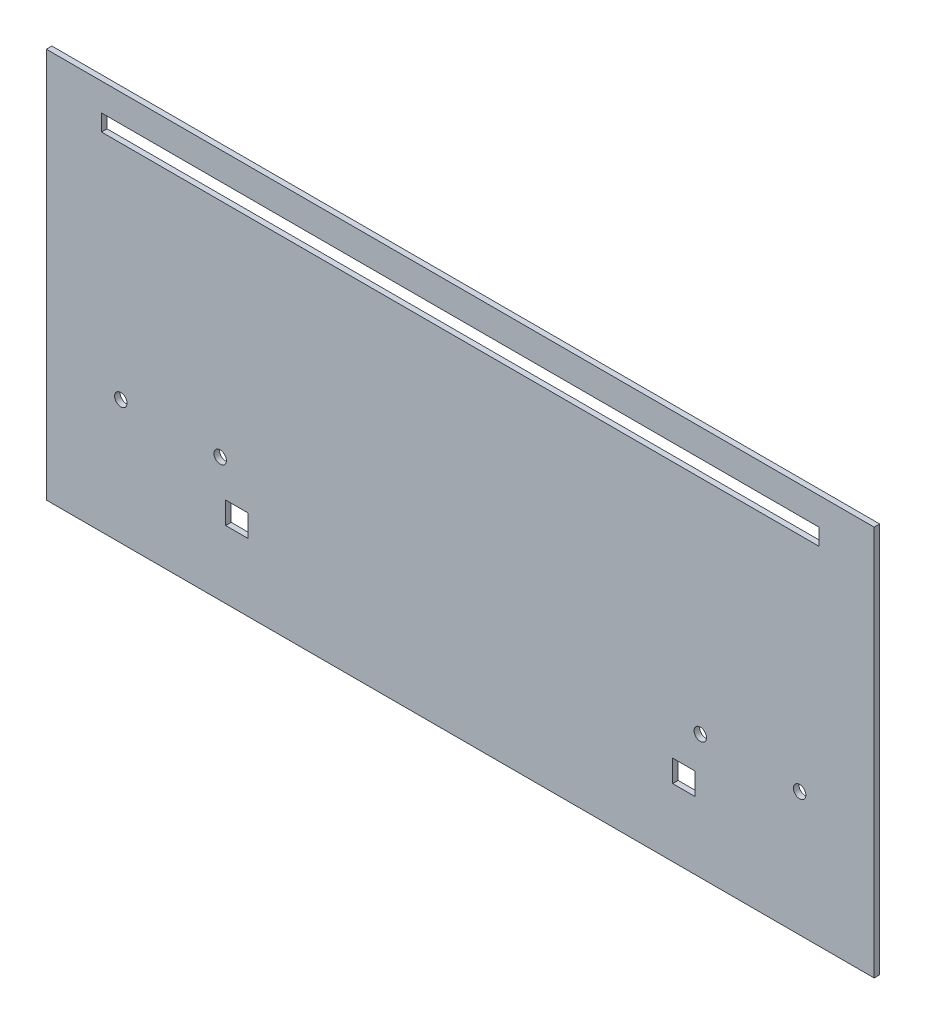
SolidWorks part; units mm, degrees
ref_plane "Front Plane" through (0, 0, 0) normal (0, 0, 1) x (1, 0, 0)
ref_plane "Top Plane" through (0, 0, 0) normal (0, 1, 0) x (1, 0, 0)
ref_plane "Right Plane" through (0, 0, 0) normal (1, 0, 0) x (0, 0, -1)
sketch "SK_Panel" plane through (0, 0, 0) normal (0, 0, 1) x (1, 0, 0)
  line L1 (-150, 0) -> (150, 0)
  line L2 (-150, 0) -> (-150, 141.5)
  line L3 (-150, 141.5) -> (150, 141.5)
  line L4 (150, 0) -> (150, 141.5)
  dimension "D1" = 300
  dimension "D2" = 141.5
  dimension "D3" = 150
extrude "EX_Panel" add sketch "SK_Panel" along normal blind 2
sketch "SK_LightSlot" plane through (0, 0, 0) normal (0, 0, 1) x (1, 0, 0)
  line L1 (-130, 125.5) -> (130, 125.5)
  line L2 (-130, 125.5) -> (-130, 131.5)
  line L3 (-130, 131.5) -> (130, 131.5)
  line L4 (130, 125.5) -> (130, 131.5)
  dimension "D1" = 260
  dimension "D2" = 6
  dimension "D3" = 130
  dimension "D4" = 125.5
extrude "CUT_LightSlot" cut sketch "SK_LightSlot" along normal blind 2
sketch "SK_CliffBolts" plane through (0, 0, 0) normal (0, 0, 1) x (1, 0, 0)
  circle A0 centre (123, 45) radius 2.25
  circle A1 centre (87, 45) radius 2.25
  circle A2 centre (-123, 45) radius 2.25
  circle A3 centre (-87, 45) radius 2.25
  dimension "D3" = 4.5
  dimension "D6" = 4.5
  dimension "D9" = 4.5
  dimension "D12" = 4.5
  dimension "D1" = 123
  dimension "D2" = 45
  dimension "D4" = 87
  dimension "D5" = 45
  dimension "D7" = 123
  dimension "D8" = 45
  dimension "D10" = 87
  dimension "D11" = 45
extrude "CUT_CliffBolts" cut sketch "SK_CliffBolts" along normal blind 2
sketch "SK_CliffCables" plane through (0, 0, 0) normal (0, 0, 1) x (1, 0, 0)
  line L1 (77, 24.5) -> (85, 24.5)
  line L2 (77, 24.5) -> (77, 32.5)
  line L3 (77, 32.5) -> (85, 32.5)
  line L4 (85, 24.5) -> (85, 32.5)
  line L6 (-85, 24.5) -> (-77, 24.5)
  line L7 (-85, 24.5) -> (-85, 32.5)
  line L8 (-85, 32.5) -> (-77, 32.5)
  line L9 (-77, 24.5) -> (-77, 32.5)
  dimension "D1" = 8
  dimension "D2" = 8
  dimension "D3" = 77
  dimension "D4" = 24.5
  dimension "D5" = 8
  dimension "D6" = 8
  dimension "D7" = 85
  dimension "D8" = 24.5
extrude "CUT_CliffCables" cut sketch "SK_CliffCables" along normal blind 2
ref_axis "AX_X" through (0, 0, -0.1) along (0, 0, 1)
ref_axis "AX_Y" through (165, 0, 0) along (-1, 0, 0)
ref_axis "AX_Z" through (0, 148.575, 0) along (0, -1, 0)
equation "\"BODY_L\"= 420"
equation "\"BODY_W\"= 340"
equation "\"FLOOR_Z\"= 35"
equation "\"DECK_Z\"= 180"
equation "\"DECK_T\"= 2"
equation "\"GRID\"= 20"
equation "\"PROFILE\"= 20"
equation "\"SM_T\"= 1.5"
equation "\"PAN_T\"= 1.5"
equation "\"PAN_TOP\"= \"FLOOR_Z\" + \"PAN_T\""
equation "\"RAIL_Y\"= 140"
equation "\"RAIL_X\"= \"BODY_L\" / 2 - \"PROFILE\" / 2 - 2"
equation "\"BOTRING_Z\"= \"PAN_TOP\" + \"PROFILE\" / 2"
equation "\"TOPRING_Z\"= \"DECK_Z\" - \"DECK_T\" - \"PROFILE\" / 2"
equation "\"DRAWER_Z\"= 93"
equation "\"MIDX_Z\"= \"DRAWER_Z\" - \"SM_T\" - \"PROFILE\" / 2"
equation "\"SKIN_Y\"= \"RAIL_Y\" + \"PROFILE\" / 2"
equation "\"SKIN_T\"= 2"
equation "\"WHEEL_D\"= 144"
equation "\"WHEEL_W\"= 52"
equation "\"TRACK\"= 365"
equation "\"AXLE_Z\"= \"WHEEL_D\" / 2"
equation "\"WHEEL_WEB_OFF\"= 6"
equation "\"HUB_T\"= 8"
equation "\"BUSHING_L\"= 6"
equation "\"HUB_GAP\"= 1"
equation "\"MOTOR_UP\"= 7"
equation "\"MOTOR_FACE_Y\"= \"TRACK\" / 2 + \"WHEEL_WEB_OFF\" - (\"BUSHING_L\" + \"HUB_GAP\" + \"HUB_T\")"
equation "\"MOTOR_AXIS_Z\"= \"AXLE_Z\" + \"MOTOR_UP\""
equation "\"CASTER_D\"= 50"
equation "\"CASTER_X\"= 150"
equation "\"CASTER_H\"= 68"
equation "\"POST_X\"= -40"
equation "\"POST_DY\"= 120"
equation "\"POST_SIZE\"= 20"
equation "\"POST_TOP\"= 400"
equation "\"BRACE_Z\"= 335"
equation "\"STRUT_X0\"= -140"
equation "\"HEAD_X0\"= -110"
equation "\"HEAD_X1\"= 12"
equation "\"BEZEL_T\"= 3"
equation "\"WEDGE_MID\"= 7.7"
equation "\"OAK_D\"= 22.9"
equation "\"HEAD_W\"= 210"
equation "\"HEAD_Z0\"= \"POST_TOP\""
equation "\"HEAD_TOP\"= 525"
equation "\"HEAD_TOP_X\"= -20"
equation "\"SCREEN_ANG\"= 35"
equation "\"LENS_X\"= 45.6"
equation "\"LENS_Z\"= 450"
equation "\"OAK_TILT\"= 5"
equation "\"OAK_VFOV_DEPTH\"= 79.5"
equation "\"OAK_VFOV_RGB\"= 72"
equation "\"LIDAR_X\"= 110"
equation "\"SCAN_Z\"= 260"
equation "\"STRUT_Z\"= \"SCAN_Z\" - 20"
equation "\"LIDAR_SCAN_H\"= 27.2"
equation "\"LIDAR_MOUNT_Z\"= \"SCAN_Z\" - \"LIDAR_SCAN_H\""
equation "\"ESTOP_X\"= -172.5"
equation "\"ESTOP_Y\"= -127.5"
equation "\"ESTOP_TOP\"= 225"
equation "\"BUMPER_T\"= 15"
equation "\"BUMPER_Z0\"= 40"
equation "\"BUMPER_Z1\"= 130"
equation "\"CLIFF_X\"= 218"
equation "\"CLIFF_Y\"= 105"
equation "\"CLIFF_Z\"= 72"
equation "\"CLIFF_ANG\"= 50"
equation "\"CONTACT_X\"= 216"
equation "\"CONTACT_Y\"= 64"
equation "\"CONTACT_Z\"= 30"
equation "\"DOCK_TAG_DIST\"= 250"
equation "\"DOCK_TAG_SIZE\"= 80"
equation "\"DOCK_TAG_Z\"= 400"
equation "\"BAT_L\"= 240"
equation "\"BAT_W\"= 90"
equation "\"BAT_H\"= 58"
equation "\"BAT_Z\"= \"DRAWER_Z\" + \"SM_T\""
equation "\"BAT_X\"= 0"
equation "\"PCB_L\"= 95"
equation "\"PCB_W\"= 120"
equation "\"PCB_H\"= 40"
equation "\"PCB_X\"= 62.5"
equation "\"DRV_X\"= 85"
equation "\"DRV_Y\"= 100"
equation "\"DRV_S\"= 50"
equation "\"COMPUTE_X\"= -65"
equation "\"COMPUTE_L\"= 90"
equation "\"COMPUTE_W\"= 160"
equation "\"D1@SK_Panel\" = 2 * (\"RAIL_Y\" + \"PROFILE\" / 2)"
equation "\"D2@SK_Panel\" = \"TOPRING_Z\" + \"PROFILE\" / 2 - \"PAN_TOP\""
equation "\"D3@SK_Panel\" = \"RAIL_Y\" + \"PROFILE\" / 2"
equation "\"D1@EX_Panel\" = \"SKIN_T\""
